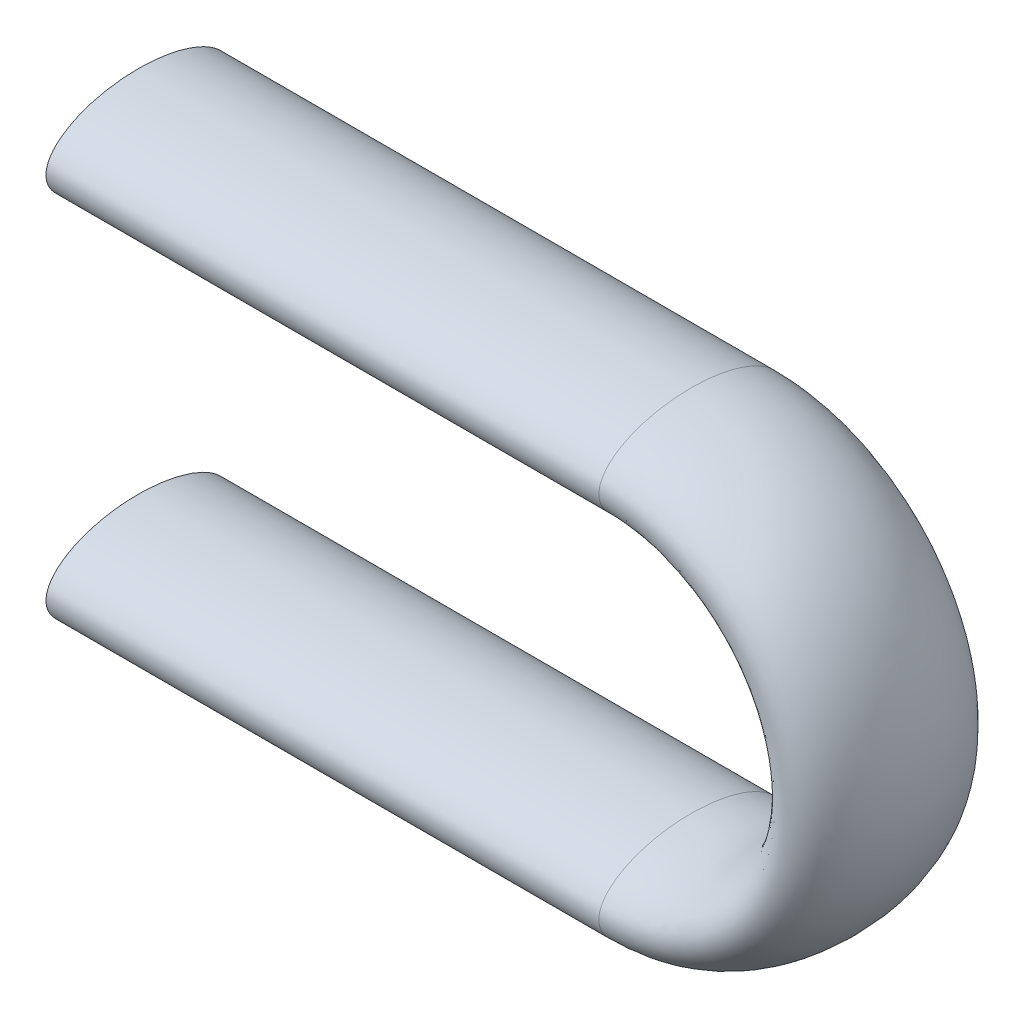
SolidWorks part; units mm, degrees
ref_plane "Front Plane" through (0, 0, 0) normal (0, 0, 1) x (1, 0, 0)
ref_plane "Top Plane" through (0, 0, 0) normal (0, 1, 0) x (1, 0, 0)
ref_plane "Right Plane" through (0, 0, 0) normal (1, 0, 0) x (0, 0, -1)
sketch "Sketch1" plane through (0, 0, 0) normal (0, 0, 1) x (1, 0, 0)
  line L0 (0, 0) -> (304.8, 0)
  line L1 (0, -203.2) -> (304.8, -203.2)
  arc A0 (304.8, 0) -> (304.8, -203.2) centre (304.8, -101.6) cw
  point P6 (0, 0)
  point P7 (0, 0)
  point P8 (0, 0)
  dimension "D1" = 101.6
  dimension "D2" = 304.8
sketch "Sketch2" plane through (0, 0, 0) normal (1, 0, 0) x (0, 0, -1)
  ellipse E0 centre (0, 0) end of major axis (-50.8, 0) minor radius 25.4
  point P1 (0, 0)
  dimension "D1" = 101.6
  dimension "D2" = 50.8
sweep "Sweep1" add profiles "Sketch2" path "Sketch1"
sketch "Sketch3" plane through (0, 0, 0) normal (-1, 0, 0) x (0, 0, 1)
  circle A0 centre (0, 0) radius 19.05
  dimension "D1" = 38.1
sweep "Cut-Sweep1" cut profiles "Sketch3" path "Sketch1<4>"
sketch "Sketch1<4>" plane through (0, 0, 0) normal (0, 0, 1) x (1, 0, 0) same geometry as "Sketch1"
